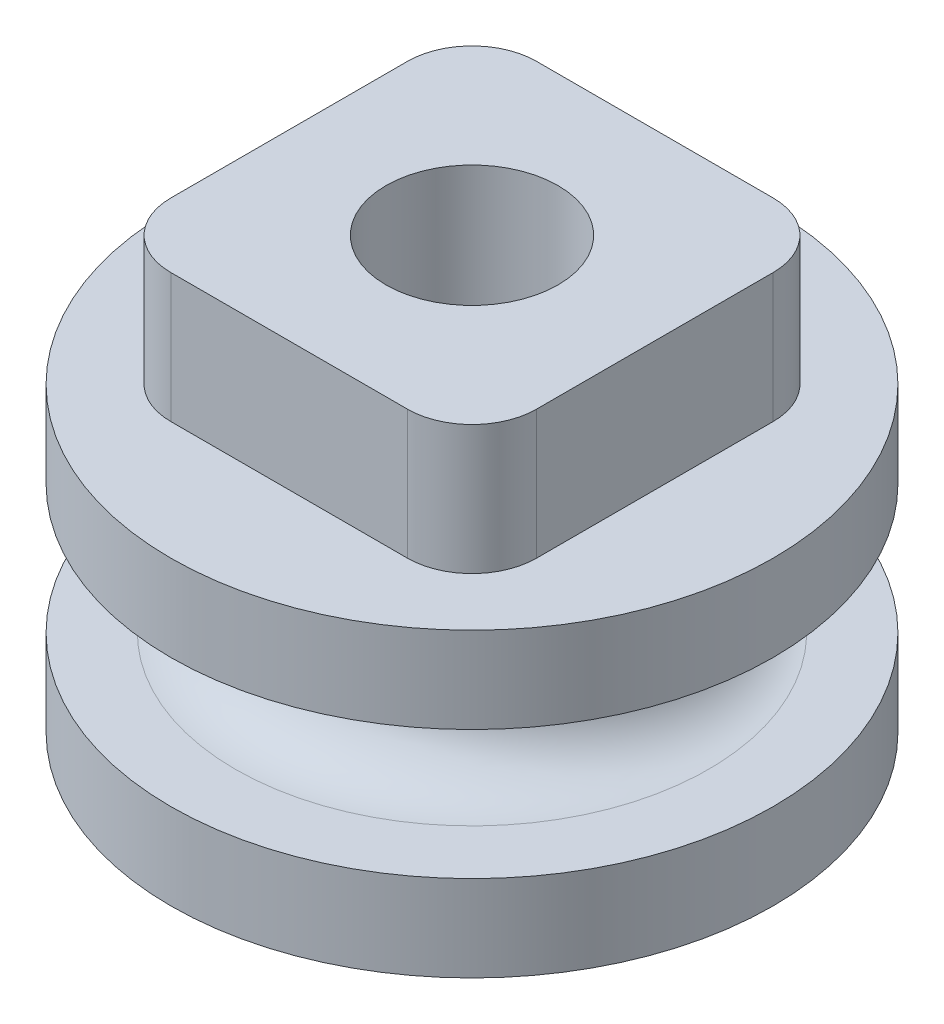
SolidWorks part; units mm, degrees
material "ABS"
ref_plane "正面" through (0, 0, 0) normal (0, 0, 1) x (1, 0, 0)
ref_plane "平面" through (0, 0, 0) normal (0, 1, 0) x (1, 0, 0)
ref_plane "右側面" through (0, 0, 0) normal (1, 0, 0) x (0, 0, -1)
sketch "ｽｹｯﾁ1" plane through (0, 0, 0) normal (0, 0, 1) x (1, 0, 0)
  line L0 (0, 0) -> (0, 6) construction
  line L1 (0, 3.5) -> (-7, 3.5)
  line L2 (-7, 3.5) -> (-7, 1.5)
  line L3 (-7, 1.5) -> (-5.5, 1.5)
  line L4 (-4, 0) -> (0, 0) construction
  line L5 (-7, -3.5) -> (-7, -1.5)
  line L6 (-7, -1.5) -> (-5.5, -1.5)
  line L7 (0, -3.5) -> (-7, -3.5)
  line L8 (0, 3.5) -> (0, -3.5)
  arc A0 (-5.5, 1.5) -> (-5.5, -1.5) centre (-5.5, 0) cw
  dimension "D1" = 3.5
  dimension "D2" = 1.5
  dimension "D3" = 4
  dimension "D4" = 7
revolve "回転1" add sketch "ｽｹｯﾁ1" angle 360 about L8
sketch "ｽｹｯﾁ2" plane through (0, -3.5, 0) normal (0, -1, 0) x (1, 0, 0)
  circle A0 centre (0, 0) radius 2
  dimension "D1" = 4
extrude "ｶｯﾄ - 押し出し1" cut sketch "ｽｹｯﾁ2" against normal through all
sketch "ｽｹｯﾁ4" plane through (0, 3.5, 0) normal (0, 1, 0) x (1, 0, 0)
  line L1 (-4.25, 4.25) -> (4.25, 4.25)
  line L2 (-4.25, 4.25) -> (-4.25, -4.25)
  line L3 (-4.25, -4.25) -> (4.25, -4.25)
  line L4 (4.25, 4.25) -> (4.25, -4.25)
  line L5 (-4.25, 4.25) -> (4.25, -4.25) construction
  line L6 (-4.25, -4.25) -> (4.25, 4.25) construction
  circle A0 centre (0, 0) radius 2 construction
  circle A1 centre (0, 0) radius 2
  point P0 (0, 0)
  dimension "D1" = 8.5
  dimension "D2" = 8.5
extrude "ﾎﾞｽ - 押し出し1" add sketch "ｽｹｯﾁ4" along normal blind 3
fillet "ﾌｨﾚｯﾄ1" radius 1.5 4 edges at (4.25, 5, -4.25) (4.25, 5, 4.25) (-4.25, 5, 4.25) (-4.25, 5, -4.25)
